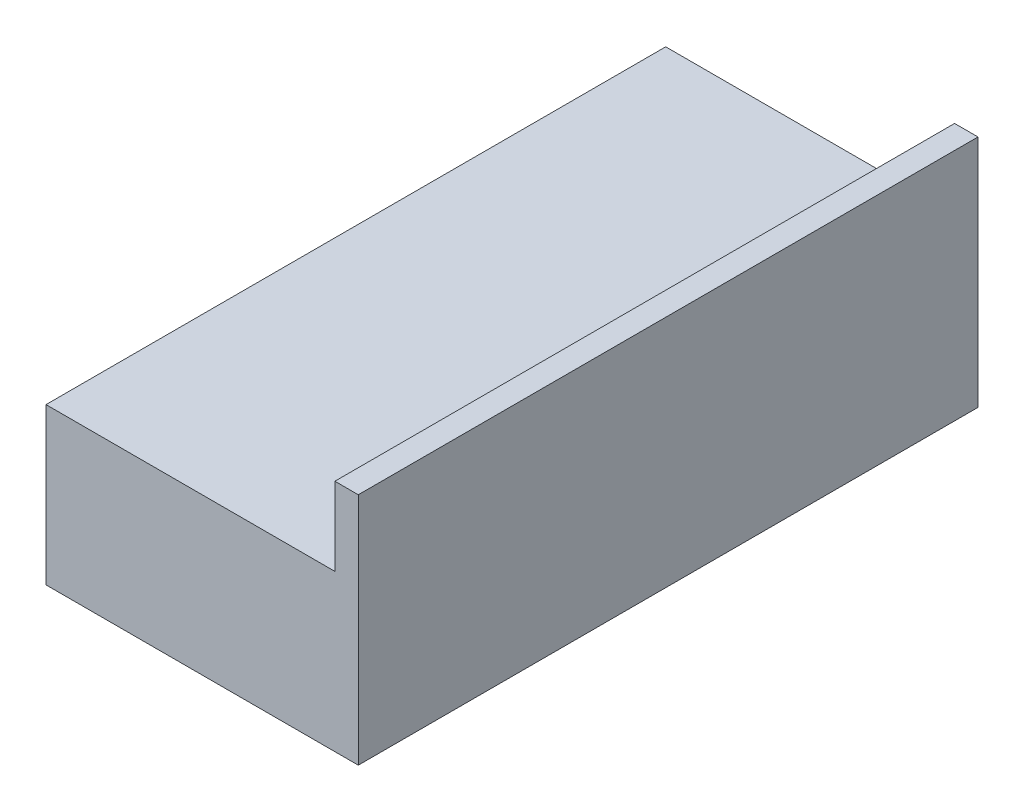
SolidWorks part; units mm, degrees
ref_plane "Front Plane" through (0, 0, 0) normal (0, 0, 1) x (1, 0, 0)
ref_plane "Top Plane" through (0, 0, 0) normal (0, 1, 0) x (1, 0, 0)
ref_plane "Right Plane" through (0, 0, 0) normal (1, 0, 0) x (0, 0, -1)
sketch "Sketch1" plane through (0, 0, 0) normal (0, 0, 1) x (1, 0, 0)
  line L1 (-20, 10) -> (17, 10)
  line L2 (-20, 10) -> (-20, -10)
  line L3 (-20, -10) -> (20, -10)
  line L4 (20, 10) -> (20, -10)
  line L5 (-20, 10) -> (20, -10) construction
  line L6 (-20, -10) -> (20, 10) construction
  line L8 (20, 10) -> (20, 20)
  line L9 (20, 20) -> (17, 20)
  line L10 (17, 10) -> (17, 20)
  point P0 (0, 0)
  point P9 (0, 0)
  dimension "D1" = 20
  dimension "D2" = 40
  dimension "D3" = 3
  dimension "D4" = 10
extrude "Boss-Extrude1" add sketch "Sketch1" along normal blind 39.6875 and the other way blind 39.6875
